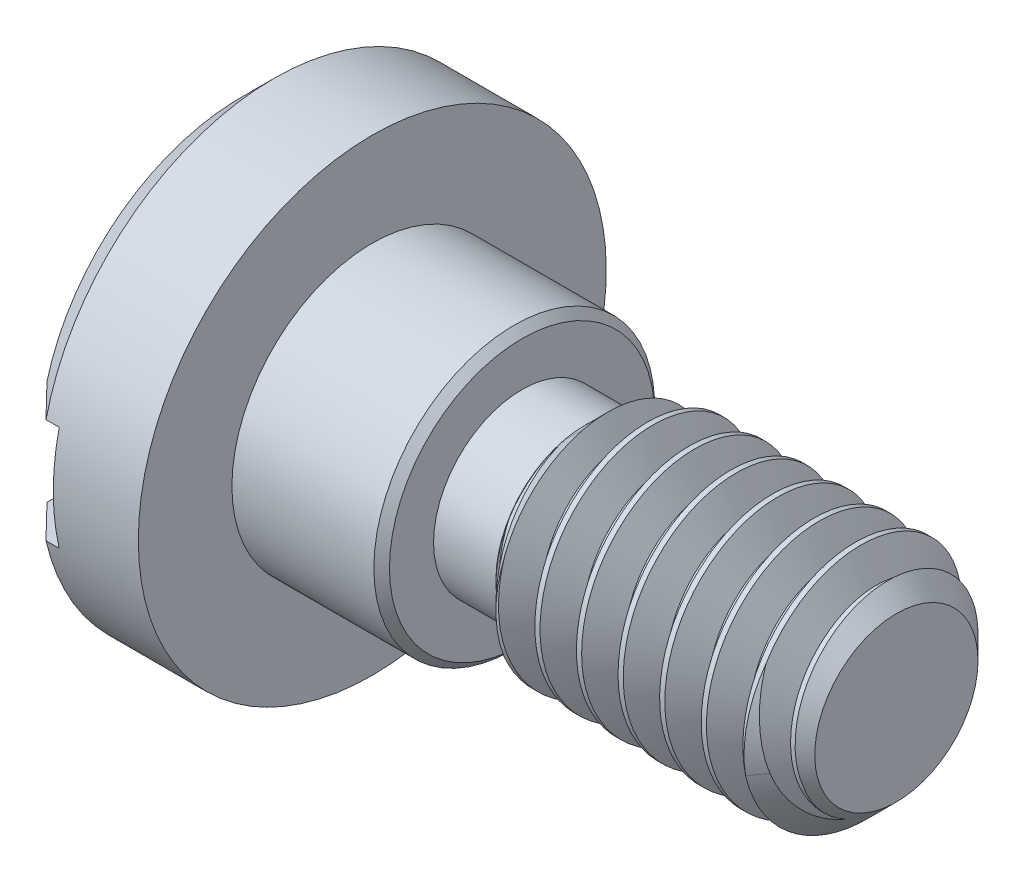
SolidWorks part; units mm, degrees
ref_plane "Front Plane" through (0, 0, 0) normal (0, 0, 1) x (1, 0, 0)
ref_plane "Top Plane" through (0, 0, 0) normal (0, 1, 0) x (1, 0, 0)
ref_plane "Right Plane" through (0, 0, 0) normal (1, 0, 0) x (0, 0, -1)
sketch "Sketch1" plane through (0, 0, 0) normal (0, 0, 1) x (1, 0, 0)
  line L0 (-11.1125, 0) -> (11.1125, 0) construction
  line L1 (-11.1125, 7.9375) -> (-11.1125, -7.9375) construction
  line L2 (-1.5875, 4.7625) -> (-1.5875, -4.7625) construction
  line L3 (11.1125, 3.9688) -> (11.1125, -3.9688) construction
  line L4 (-6.6675, 7.9375) -> (-6.6675, -7.9375) construction
  line L5 (11.1125, -3.9688) -> (11.1125, -4.7625) construction
  point P2 (6.1736, -3.9688)
  point P8 (-1.5875, 0)
  dimension "B" = 22.225
  dimension "E" = 9.525
  dimension "thread size" = 7.9375
  dimension "C" = 9.525
  dimension "D" = 5.08
  dimension "A" = 15.875
  dimension "D1" = 12.7
  dimension "D2" = 4.445
  dimension "D3" = 0.7938
  dimension "D4" = 4.9389
ref_plane "Plane1" through (11.1125, 0, 0) normal (1, 0, 0) x (0, 0, -1)
sketch "Sketch2" plane through (11.1125, 0, 0) normal (1, 0, 0) x (0, 0, -1)
  circle A0 centre (0, 0) radius 3.9688
extrude "Extrude1" add sketch "Sketch2" against normal up to vertex (12.7 mm away) up to point (-1.5875, 4.7625, 0)
sketch "Sketch3" plane through (11.1125, 0, 0) normal (1, 0, 0) x (0, 0, -1)
  circle A1 centre (0, 0) radius 3.9688
  circle A2 centre (0, 0) radius 3.9688
  dimension "D1" = 0
curve "Helix/Spiral1" pitch 1.4111 height 13.4938 turns 9.5625 parameters "pitch"=1.4111
chamfer "Chamfer1" distance 1.1994 angle 45 1 edges at (11.1125, 0, -3.9688)
sketch "Sketch4" plane through (0, 0, 0) normal (0, 0, 1) x (1, 0, 0)
  line L0 (12.3472, 3.9688) -> (11.1125, 3.9688)
  line L1 (11.1125, 3.9688) -> (11.6417, 3.0522)
  line L2 (11.6417, 3.0522) -> (11.8181, 3.0522)
  line L3 (11.8181, 3.0522) -> (12.3472, 3.9688)
  line L4 (11.7299, 3.0522) -> (11.7299, 3.9688) construction
  line L5 (12.0826, 3.5105) -> (11.3771, 3.5105) construction
  dimension "D1" = 60
  dimension "D2" = 0.1764
  dimension "D3" = 0.7056
sweep "Cut-Sweep1" cut profiles "Sketch4" path "Helix/Spiral1" align with end faces yes
sketch "Sketch5" plane through (0, 0, 0) normal (0, 0, 1) x (1, 0, 0)
  line L0 (-1.5875, 3.9687) -> (-1.5875, 3.0014)
  line L1 (-1.5875, 3.0014) -> (0.5292, 3.0014)
  line L2 (0.5292, 3.0014) -> (1.4965, 3.9687)
  line L3 (1.4965, 3.9687) -> (-1.5875, 3.9687)
  line L4 (-1.5875, 4.7625) -> (-1.5875, -4.7625) construction
  dimension "D1" = 2.1167
  dimension "D2" = 45
revolve "Cut-Revolve1" cut sketch "Sketch5" angle 360 about L0
sketch "Sketch6" plane through (-1.5875, 0, 0) normal (-1, 0, 0) x (0, 0, 1)
  circle A0 centre (0, 0) radius 4.7625
extrude "Extrude2" add sketch "Sketch6" along normal up to vertex (5.08 mm away) up to point (-6.6675, 7.9375, 0)
sketch "Sketch7" plane through (-6.6675, 0, 0) normal (-1, 0, 0) x (0, 0, 1)
  circle A0 centre (0, 0) radius 7.9375
extrude "Extrude3" add sketch "Sketch7" along normal up to vertex (4.445 mm away) up to point (-11.1125, 7.9375, 0)
chamfer "Chamfer2" distance 0.2646 angle 45 1 edges at (-1.5875, 0, 4.7625)
chamfer "Chamfer3" distance 1.1112 angle 45 1 edges at (-11.1125, 0, 7.9375)
sketch "Sketch8" plane through (-11.1125, 0, 0) normal (-1, 0, 0) x (0, 0, 1)
  line L0 (-7.9375, 0) -> (7.9375, 0)
  line L1 (0, 7.9375) -> (0, -7.9375) construction
extrude "Cut-Extrude-Thin1" cut sketch "Sketch8" against normal blind 1.5593 thin thin type mid plane wall 3.556
sketch "Sketch9" [suppressed] plane through (-5.5562, 0, 0) normal (-1, 0, 0) x (0, 0, 1)
  line L1 (0, 1.5071) -> (-1.3052, 0.7536)
  line L2 (-1.3052, 0.7536) -> (-1.3052, -0.7536)
  line L3 (-1.3052, -0.7536) -> (0, -1.5071)
  line L4 (0, -1.5071) -> (1.3052, -0.7536)
  line L5 (1.3052, -0.7536) -> (1.3052, 0.7536)
  line L6 (1.3052, 0.7536) -> (0, 1.5071)
  circle A0 centre (0, 0) radius 1.3052 construction
  dimension "Hex" = 2.6104
extrude "Extrude4" [suppressed] cut sketch "Sketch9" against normal up to surface (2.2225 mm away)
sketch "Sketch10" [suppressed] plane through (-5.5562, 0, 0) normal (-1, 0, 0) x (0, 0, 1)
  circle A0 centre (0, 0) radius 1.5071
extrude "Extrude5" [suppressed] cut sketch "Sketch10" against normal through all draft 45
equation "\"D2@Sketch4\" = \"pitch@Helix/Spiral1\"*.125"
equation "\"D3@Sketch4\" = \"pitch@Helix/Spiral1\"*.5"
equation "\"D1@Chamfer1\" = \"pitch@Helix/Spiral1\"*.850"
equation "\"D3@Helix/Spiral1\" = \"D1@Sketch1\"+.03125"
equation "\"D1@Sketch5\" = \"pitch@Helix/Spiral1\"*1.5"
equation "\"D1@Chamfer3\" = \"D2@Sketch1\"/4"
equation "\"D1@Cut-Extrude-Thin1\" = \"D1@Chamfer1\"*1.3"
equation "\"D1@Chamfer2\" = \"D3@Sketch1\"/3"
equation "\"D5@Cut-Extrude-Thin1\" = \"D2@Sketch1\"*.8"
equation "\"D4@Sketch1\" = \"pitch@Helix/Spiral1\"*3.50"
